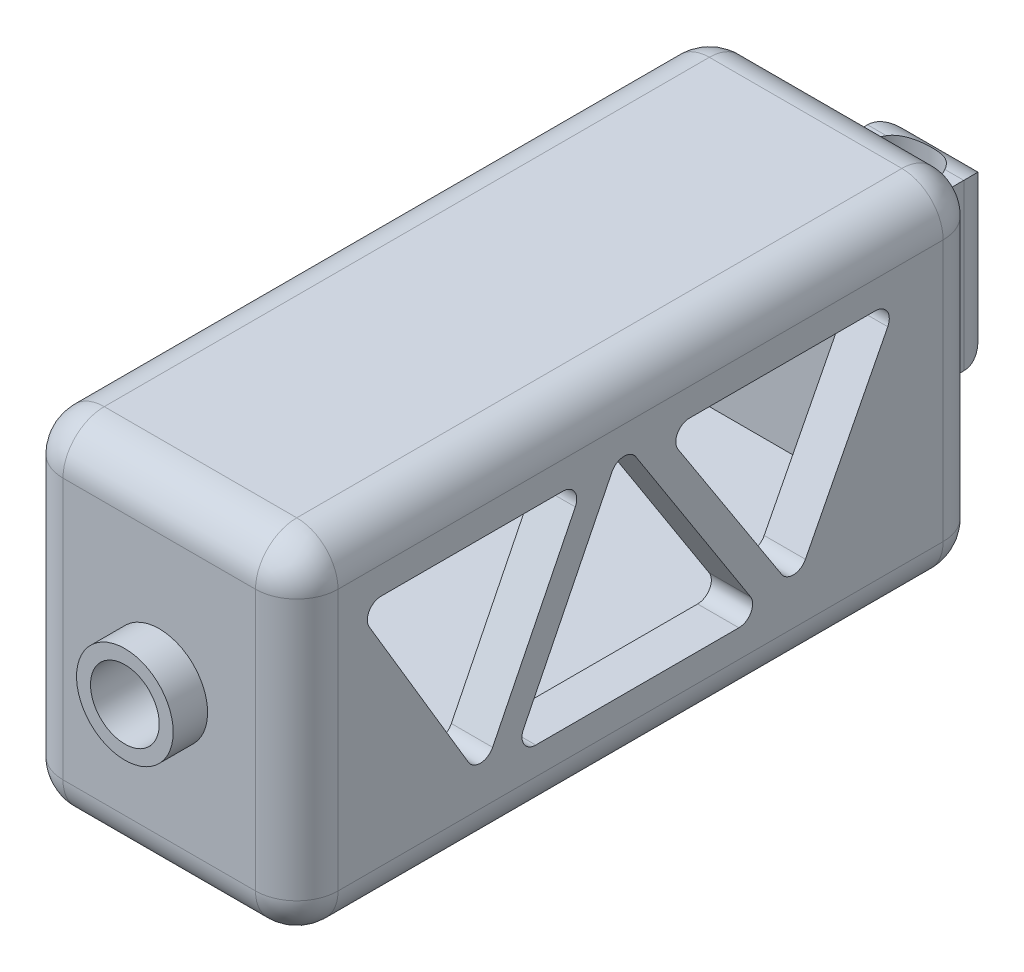
SolidWorks part; units mm, degrees
ref_plane "Front Plane" through (0, 0, 0) normal (0, 0, 1) x (1, 0, 0)
ref_plane "Top Plane" through (0, 0, 0) normal (0, 1, 0) x (1, 0, 0)
ref_plane "Right Plane" through (0, 0, 0) normal (1, 0, 0) x (0, 0, -1)
sketch "Sketch1" plane through (0, 0, 0) normal (1, 0, 0) x (0, 0, -1)
  line L1 (-50, 25) -> (50, 25)
  line L2 (-50, 25) -> (-50, -25)
  line L3 (-50, -25) -> (50, -25)
  line L4 (50, 25) -> (50, -25)
  line L5 (-50, 25) -> (50, -25) construction
  line L6 (-50, -25) -> (50, 25) construction
  point P0 (0, 0)
  dimension "D1" = 50
  dimension "D2" = 100
extrude "Boss-Extrude1" add sketch "Sketch1" along normal blind 40
fillet "Fillet1" radius 6 12 edges at (0, -25, 0) (0, 0, -50) (20, -25, -50) (40, -25, 0) (40, 0, -50) (40, 25, 0) (20, 25, -50) (0, 25, 0) (20, -25, 50) (0, 0, 50) (20, 25, 50) (40, 0, 50)
sketch "Sketch4" plane through (0, 0, 50) normal (0, 0, 1) x (1, 0, 0)
  line L0 (20, 19) -> (20, -19) construction
  line L1 (34, 19) -> (6, 19) construction
  line L2 (6, -19) -> (34, -19) construction
  line L3 (6, 0) -> (34, 0) construction
  line L4 (6, 19) -> (6, -19) construction
  line L5 (34, -19) -> (34, 19) construction
  circle A0 centre (20, 0) radius 5
  dimension "D1" = 10
extrude "Cut-Extrude2" cut sketch "Sketch4" against normal blind 8
sketch "Sketch27" plane through (0, 0, 0) normal (-1, 0, 0) x (0, 0, 1)
  line L2 (-44, -19) -> (44, -19) construction
  line L4 (-35.9487, 12.0857) -> (-23.9738, -11.2125)
  line L5 (-34.1699, 15) -> (-7.1198, 15)
  line L6 (-5.4407, 11.9135) -> (-20.5159, -11.3847)
  line L7 (44, 19) -> (-44, 19) construction
  line L9 (4.169, 13.8395) -> (17.0352, -12.1116)
  line L11 (9.4903, 12.1116) -> (21.5181, -12.1485)
  line L12 (25.0289, -12.2824) -> (39.4561, 11.9777)
  line L13 (37.7371, 15) -> (11.2821, 15)
  line L18 (-14.292, -15) -> (15.2433, -15)
  line L20 (0.6994, 14.0397) -> (-15.9748, -11.9191)
  arc A3 (-34.1699, 15) -> (-35.9487, 12.0857) centre (-34.1699, 13) ccw
  arc A4 (-7.1198, 15) -> (-5.4407, 11.9135) centre (-7.1198, 13) cw
  arc A5 (-20.5159, -11.3847) -> (-23.9738, -11.2125) centre (-22.195, -10.2982) cw
  arc A7 (4.169, 13.8395) -> (0.6994, 14.0397) centre (2.3772, 12.9511) ccw
  arc A9 (9.4903, 12.1116) -> (11.2821, 15) centre (11.2821, 13) cw
  arc A10 (37.7371, 15) -> (39.4561, 11.9777) centre (37.7371, 13) cw
  arc A11 (25.0289, -12.2824) -> (21.5181, -12.1485) centre (23.3099, -11.2601) cw
  arc A12 (-14.292, -15) -> (-15.9748, -11.9191) centre (-14.292, -13) cw
  arc A13 (15.2433, -15) -> (17.0352, -12.1116) centre (15.2433, -13) ccw
  point P9 (-44, 19)
  point P12 (-24.4686, -19)
  point P15 (-44, -19)
  point P32 (-20.679, -19)
  point P37 (20.43, -19)
  dimension "D5" = 2
  dimension "D6" = 2
  dimension "D7" = 2
  dimension "D10" = 2
  dimension "D11" = 2
  dimension "D12" = 4
  dimension "D14" = 2
  dimension "D15" = 2
  dimension "D16" = 2
  dimension "D9" = 2
  dimension "D8" = 4
  dimension "D13" = 4
  dimension "D17" = 4
extrude "Cut-Extrude4" cut sketch "Sketch27" against normal through all
sketch "Sketch29" plane through (0, 0, -50) normal (0, 0, -1) x (-1, 0, 0)
  line L0 (-20, 19) -> (-20, -9.0034) construction
  line L1 (-6, 19) -> (-34, 19) construction
  line L2 (-6, 0) -> (-20, 0) construction
  line L3 (-6, -19) -> (-6, 19) construction
  line L4 (-34, 19) -> (-34, -19) construction
  line L5 (-27, 12) -> (-13, 12)
  line L6 (-27, 12) -> (-27, -12)
  line L7 (-27, -12) -> (-13, -12)
  line L8 (-13, 12) -> (-13, -12)
  line L9 (-27, 12) -> (-13, -12) construction
  line L10 (-27, -12) -> (-13, 12) construction
  dimension "D1" = 7
  dimension "D2" = 7
extrude "Boss-Extrude2" add sketch "Sketch29" along normal blind 15
sketch "Sketch31" plane through (0, -12, 0) normal (0, -1, 0) x (1, 0, 0)
  circle A0 centre (20, -57.5) radius 4.9383
extrude "Cut-Extrude6" cut sketch "Sketch31" against normal through all
fillet "Fillet7" radius 5 4 edges at (20, -12, -65) (27, 0, -65) (20, 12, -65) (13, 0, -65)
ref_plane "Plane1" through (0, 0, 44) normal (0, 0, 1) x (1, 0, 0)
sketch "Sketch32" plane through (0, 0, 44) normal (0, 0, 1) x (1, 0, 0)
  line L1 (6, 19) -> (34, 19)
  line L2 (6, 19) -> (6, -19)
  line L3 (6, -19) -> (34, -19)
  line L4 (34, 19) -> (34, -19)
extrude "Cut-Extrude7" cut sketch "Sketch32" against normal blind 88
sketch "Sketch33" plane through (0, 0, 50) normal (0, 0, 1) x (1, 0, 0)
  circle A0 centre (20, 0) radius 7.0297
  circle A1 centre (20, 0) radius 5
extrude "Boss-Extrude3" add sketch "Sketch33" along normal blind 5
sketch "Sketch20" plane through (0, 25, 0) normal (0, 1, 0) x (1, 0, 0)
